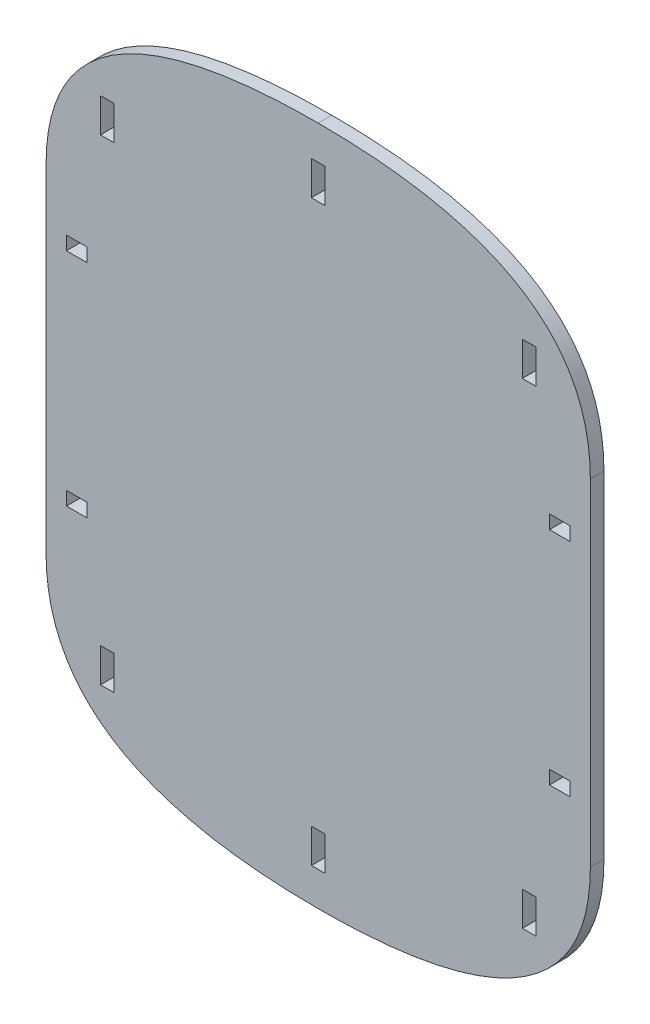
SolidWorks part; units mm, degrees
ref_plane "Front Plane" through (0, 0, 0) normal (0, 0, 1) x (1, 0, 0)
ref_plane "Top Plane" through (0, 0, 0) normal (0, 1, 0) x (1, 0, 0)
ref_plane "Right Plane" through (0, 0, 0) normal (1, 0, 0) x (0, 0, -1)
sketch "Sketch1" plane through (0, 0, 0) normal (0, 0, 1) x (1, 0, 0)
  line L1 (0, 0) -> (203.2, 0)
  line L2 (0, 0) -> (0, 254)
  line L3 (0, 254) -> (203.2, 254)
  line L4 (203.2, 0) -> (203.2, 254)
  dimension "D1" = 254
extrude "Boss-Extrude1" add sketch "Sketch1" along normal blind 5.08
fillet "Fillet1" radius 64.2197 4 edges at (203.2, 254, 2.54) (0, 254, 2.54) (203.2, 0, 2.54) (0, 0, 2.54)
sketch "Sketch5" plane through (0, 0, 5.08) normal (0, 0, 1) x (1, 0, 0)
  line L1 (61.238, 129.1944) -> (140.74, 129.1944) construction
  line L2 (61.238, 129.1944) -> (61.238, 206.9184) construction
  line L3 (61.238, 206.9184) -> (140.74, 206.9184) construction
  line L4 (140.74, 129.1944) -> (140.74, 206.9184) construction
  dimension "D1" = 79.502
  dimension "D2" = 77.724
sketch "Sketch6" plane through (0, 0, 5.08) normal (0, 0, 1) x (1, 0, 0)
  line L1 (-299.8233, 201.2984) -> (-270.6133, 201.2984) construction
  line L2 (-299.8233, 201.2984) -> (-299.8233, 103.2544) construction
  line L3 (-299.8233, 103.2544) -> (-270.6133, 103.2544) construction
  line L4 (-270.6133, 201.2984) -> (-270.6133, 103.2544) construction
  dimension "D1" = 29.21
  dimension "D2" = 98.044
ref_plane "Plane1" through (101.6, 0, 0) normal (-1, 0, 0) x (0, 0, 1)
sketch "Sketch12" plane through (0, 0, 5.08) normal (0, 0, 1) x (1, 0, 0)
  line L0 (0, 147.066) -> (203.2, 147.066) construction
  line L1 (0, 106.934) -> (203.2, 106.934) construction
  line L2 (0, 127) -> (203.2, 127) construction
  line L3 (0, 189.7803) -> (0, 64.2197) construction
  line L5 (203.2, 64.2197) -> (203.2, 189.7803) construction
  dimension "D1" = 40.132
  dimension "D2" = 20.066
sketch "Sketch11" plane through (0, 0, 5.08) normal (0, 0, 1) x (1, 0, 0)
  line L0 (101.6, 254) -> (101.6, 0) construction
  line L1 (101.6, 254) -> (101.6, 310.8871) construction
  line L2 (101.6, 0) -> (101.6, -58.1405) construction
sketch "Sketch13" plane through (0, 0, 5.08) normal (0, 0, 1) x (1, 0, 0)
  line L8 (101.6, 215.9) -> (177.8, 215.9) construction
  line L25 (101.6, 38.1) -> (177.8, 38.1) construction
  line L27 (25.4, 215.9) -> (101.6, 215.9) construction
  line L28 (25.4, 222.25) -> (20.32, 222.25)
  line L29 (0, 127) -> (203.2, 127) construction
  line L30 (101.6, 254) -> (101.6, 0) construction
  line L39 (20.32, 222.25) -> (20.32, 209.55)
  line L40 (25.4, 38.1) -> (101.6, 38.1) construction
  line L41 (20.32, 209.55) -> (25.4, 209.55)
  line L45 (25.4, 222.25) -> (25.4, 215.9)
  line L46 (25.4, 215.9) -> (25.4, 209.55)
  line L47 (177.8, 215.9) -> (177.8, 222.25)
  line L48 (177.8, 222.25) -> (182.88, 222.25)
  line L49 (182.88, 222.25) -> (182.88, 209.55)
  line L50 (182.88, 209.55) -> (177.8, 209.55)
  line L51 (177.8, 209.55) -> (177.8, 215.9)
  line L52 (177.8, 38.1) -> (177.8, 44.45)
  line L53 (177.8, 44.45) -> (182.88, 44.45)
  line L54 (182.88, 44.45) -> (182.88, 31.75)
  line L55 (182.88, 31.75) -> (177.8, 31.75)
  line L56 (177.8, 31.75) -> (177.8, 38.1)
  line L57 (25.4, 38.1) -> (25.4, 44.45)
  line L58 (25.4, 44.45) -> (20.32, 44.45)
  line L59 (20.32, 44.45) -> (20.32, 31.75)
  line L60 (20.32, 31.75) -> (25.4, 31.75)
  line L61 (25.4, 31.75) -> (25.4, 38.1)
  line L62 (182.88, 209.55) -> (182.88, 168.275) construction
  line L63 (182.88, 168.275) -> (182.88, 127) construction
  line L64 (182.88, 127) -> (182.88, 85.725) construction
  line L65 (182.88, 85.725) -> (182.88, 44.45) construction
  line L66 (20.32, 209.55) -> (20.32, 168.275) construction
  line L67 (20.32, 168.275) -> (20.32, 127) construction
  line L68 (20.32, 127) -> (20.32, 85.725) construction
  line L69 (20.32, 85.725) -> (20.32, 44.45) construction
  line L70 (182.88, 168.275) -> (187.96, 168.275) construction
  line L71 (182.88, 85.725) -> (187.96, 85.725) construction
  line L72 (20.32, 168.275) -> (15.24, 168.275) construction
  line L73 (20.32, 85.725) -> (15.24, 85.725) construction
  line L74 (187.96, 168.275) -> (187.96, 165.735)
  line L75 (187.96, 165.735) -> (195.58, 165.735)
  line L76 (195.58, 165.735) -> (195.58, 170.815)
  line L77 (195.58, 170.815) -> (187.96, 170.815)
  line L78 (187.96, 170.815) -> (187.96, 168.275)
  line L79 (187.96, 85.725) -> (187.96, 88.265)
  line L80 (187.96, 88.265) -> (195.58, 88.265)
  line L81 (195.58, 88.265) -> (195.58, 83.185)
  line L82 (195.58, 83.185) -> (187.96, 83.185)
  line L83 (187.96, 83.185) -> (187.96, 85.725)
  line L84 (15.24, 168.275) -> (15.24, 170.815)
  line L85 (15.24, 170.815) -> (7.62, 170.815)
  line L86 (7.62, 170.815) -> (7.62, 165.735)
  line L87 (7.62, 165.735) -> (15.24, 165.735)
  line L88 (15.24, 165.735) -> (15.24, 168.275)
  line L89 (15.24, 85.725) -> (15.24, 88.265)
  line L90 (15.24, 88.265) -> (7.62, 88.265)
  line L91 (7.62, 88.265) -> (7.62, 83.185)
  line L92 (7.62, 83.185) -> (15.24, 83.185)
  line L93 (15.24, 83.185) -> (15.24, 85.725)
  dimension "D5" = 88.9
  dimension "D6" = 88.9
  dimension "D3" = 5.08
  dimension "D4" = 5.08
  dimension "D7" = 2.54
  dimension "D8" = 7.62
sketch "Sketch14" plane through (0, 0, 5.08) normal (0, 0, 1) x (1, 0, 0)
  line L0 (101.6, 254) -> (101.6, 0) construction
  line L1 (99.06, 241.3) -> (104.14, 241.3)
  line L2 (99.06, 241.3) -> (99.06, 228.6)
  line L3 (99.06, 228.6) -> (104.14, 228.6)
  line L4 (104.14, 241.3) -> (104.14, 228.6)
  line L5 (99.06, 25.4) -> (104.14, 25.4)
  line L6 (99.06, 25.4) -> (99.06, 12.7)
  line L7 (99.06, 12.7) -> (104.14, 12.7)
  line L8 (104.14, 25.4) -> (104.14, 12.7)
  point P8 (101.6, 241.3)
  point P15 (101.6, 25.4)
  dimension "D3" = 5.08
  dimension "D2" = 12.7
  dimension "D5" = 12.7
  dimension "D6" = 12.7
extrude "Cut-Extrude2" cut sketch "Sketch14" against normal through all
extrude "Cut-Extrude3" cut sketch "Sketch13" against normal through all
equation "\"FoamCore\" = \".2\""
equation "\"MDF\" = \".2\""
equation "\"GMaterial\"= \".2\""
equation "\"PVCMountDiameter\" = \"0.5in\""
equation "\"PVCMountDistanceToEdge\" = \"0.5\""
equation "\"PVCThickness\" = \"0.13in\""
equation "\"BaseWidth\" = \"8in\""
equation "\"BaseLength\" = \"10in\""
equation "\"BallDiameter\" = \"38mm\""
equation "\"BaseGap\" = \"4in\""
equation "\"FunnelTopDiameter\" = \"8in\""
equation "\"FunnelTopDepth\" = \"0.5in\""
equation "\"BallGap\" = \"0.1in\""
equation "\"FunnelLength\" = 3in"
equation "\"FunnelMaterial\" = 0.1in"
equation "\"FunnelLowerDiameter\" = 1.9in"
equation "\"FunnelDepth\" = 1.5in"
equation "\"AmmoFeederLength\" = 1.5in + 76mm"
equation "\"AmmoFeederCutoffLength\"= \"MovingWheelDiameter\""
equation "\"WheelThickness\" = 0.5in"
equation "\"LauncherWheelDiameter\" = 76mm"
equation "\"MotorFrontLength\" = 0.95in"
equation "\"MotorBodyTotalLength\" = 2.03in"
equation "\"MotorFrontDiameter\" = 1.5in"
equation "\"MotorLowerDriveshaftDiameter\" = 0.46in"
equation "\"MotorLowerDriveshaftThickness\" = 0.25in"
equation "\"MotorFullDriveshaftLength\" = 0.78in"
equation "\"MotorDriveshaftDiameter\" = 0.23in"
equation "\"MotorDriveshaftFlatThickness\" = 0.2in"
equation "\"MotorRearDiameter\" = 31.9mm"
equation "\"MotorDriveshaftBottomToTop\" = 31.1mm"
equation "\"MotorFlatDriveshaftLength\" = 11.7mm"
equation "\"MotorDistanceBetweenLowerandTopHoles\" = 0.5in"
equation "\"MotorMountsDistanceFromEdge\" = 0.06in"
equation "\"MotorScrewMountDiameter\" = 0.1in"
equation "\"MotorScrewMountDepth\" = 0.13in"
equation "\"HBRidgeScrewHoleDeep\" = 0.18in"
equation "\"D1@Sketch1\"=\"BaseLength\""
equation "\"D2@Sketch1\"=\"BaseWidth\""
equation "\"D1@Boss-Extrude1\"=\"MDF\""
equation "\"D1@Fillet1\"=(\"BaseLength\"/3)-(\"MotorMountWidth\"/2)"
equation "\"FunnelBendLength\" = 2*pi*\"FunnelLowerDiameter\"/2*135"
equation "\"MotorMountWidth\" = \"1.61in\""
equation "\"HBridgeWidth\" = 2.25in"
equation "\"HBridgeLength\" = 1.40in"
equation "\"UnoWidth\" = 3.13in"
equation "\"UnoLength\" = 3.06in"
equation "\"BatteryWidth\" = 1.15in"
equation "\"D1@Sketch6\"=\"BatteryWidth\""
equation "\"BatteryLength\" = 3.86in"
equation "\"D2@Sketch6\"=\"BatteryLength\""
equation "\"MotorMountLength\" = \"1.58in\""
equation "\"MotorMountToEdgeGap\" = \"3.3mm\""
equation "\"D2@Fillet1\"=\"BaseWidth\"/2"
equation "\"ScrewDiameter\" = 2.7mm"
equation "\"MotorMountToMountWidthGap\" = \"25.8mm\""
equation "\"MotorMountToMountLengthGap\" = \"20.5mm\""
equation "\"MotorMountToInsideEdgeGap\" = \"6.5mm\""
equation "\"MotorMountMaterialThickness\" = 1.6mm"
equation "\"MotorMountBaseScrewholeDiameter\" = 3.8mm"
equation "\"MotorMountBaseDistancebetweenHoles\" = 0.8in"
equation "\"MotorMountHeight\" = 1.85in"
equation "\"MotorMountFaceScrewtoBase\" = 0.46in"
equation "\"MotorMountFaceDistanceBetweenScrews\" = 0.95in"
equation "\"MotorMountFaceMiddletoEdge\" = 0.16in"
equation "\"MotorMountFaceBottomtoEdge\" = 0.42in"
equation "\"MotorMountCenterholeHeight\" = 1.04in"
equation "\"MotorMountCenterholetoEdge\" = 0.25in"
equation "\"MovingWheelDiameter\" = 76mm"
equation "\"MovingWheelThickness\" = 0.5in"
equation "\"D1@Sketch12\"=\"MotorMountLength\""
equation "\"D2@Sketch12\"=\"MotorMountLength\"/2"
equation "\"PVCDiameter\" = 1.5in"
equation "\"BraceLength\" = 1in"
equation "\"BraceVerticalOffset\" = 3.5in"
equation "\"BraceHorizontalOffset\" = 2.5in"
equation "\"D5@Sketch13\"=\"BraceVerticalOffset\""
equation "\"D6@Sketch13\"=\"BraceVerticalOffset\""
equation "\"D2@Sketch5\"=\"UnoLength\""
equation "\"D1@Sketch5\"=\"UnoWidth\""
equation "\"D1@Sketch14\"=\"MDF\""
equation "\"D2@Sketch14\"=\"BraceLength\"/2"
equation "\"D3@Sketch14\"=\"MDF\""
equation "\"D4@Sketch14\"=\"BraceLength\"/2"
equation "\"D5@Sketch14\"=\"BraceLength\"/2"
equation "\"D6@Sketch14\"=\"BraceLength\"/2"
equation "\"Distancebetweenwalls\" = 6in"
equation "\"D1@Sketch13\"=\"Distancebetweenwalls\"/2"
equation "\"D2@Sketch13\"=\"BraceLength\"/4"
equation "\"D3@Sketch13\"=\"MDF\""
equation "\"BaseToBaseDistance\" = 3in"
equation "\"PVCOutsideDiameter\" = \"PVCDiameter\" + 2*\"PVCThickness\""
equation "\"Slidewidth\" = 0.3in"
equation "\"Slidelength\" = 0.8in"
equation "\"Bottomtofloor\" = 0.53in"
equation "\"tabdistance\" = 0.2in"
equation "\"tabwidth\" = 0.3in"
equation "\"D4@Sketch13\"=\"tabdistance\""
equation "\"D7@Sketch13\"=\"MDF\"/2"
equation "\"D8@Sketch13\"=\"tabwidth\""
equation "\"BatteryHeight\" = 3.86in"
equation "\"MotorToEdgeGap\" = \"0.14in\""
equation "\"MotorMountToMountGap\" = \"20.5mm\""
